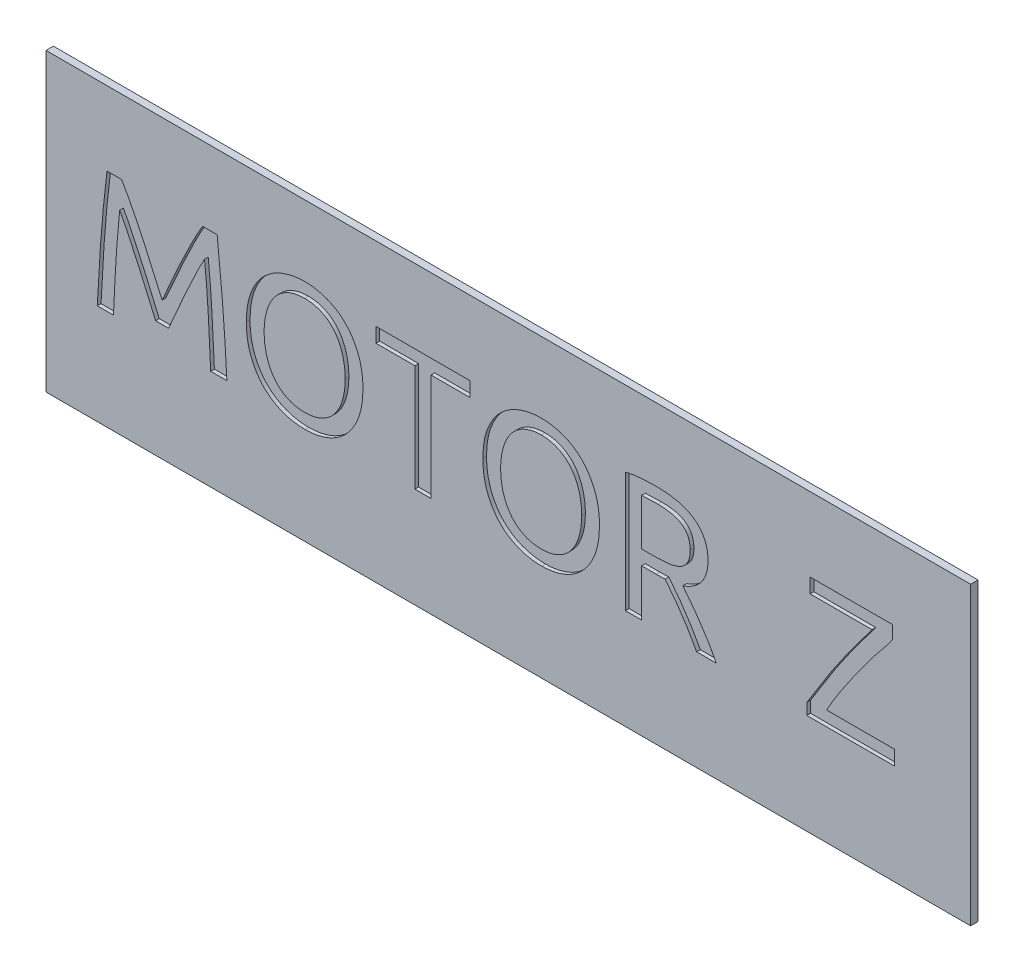
SolidWorks part; units mm, degrees
ref_plane "Front Plane" through (0, 0, 0) normal (0, 0, 1) x (1, 0, 0)
ref_plane "Top Plane" through (0, 0, 0) normal (0, 1, 0) x (1, 0, 0)
ref_plane "Right Plane" through (0, 0, 0) normal (1, 0, 0) x (0, 0, -1)
sketch "Sketch1" plane through (0, 0, 0) normal (0, 0, 1) x (1, 0, 0)
  line L1 (12.5, -4) -> (-12.5, -4)
  line L2 (12.5, -4) -> (12.5, 4)
  line L3 (12.5, 4) -> (-12.5, 4)
  line L4 (-12.5, -4) -> (-12.5, 4)
  line L5 (12.5, -4) -> (-12.5, 4) construction
  line L6 (12.5, 4) -> (-12.5, -4) construction
  point P0 (0, 0)
  dimension "D1" = 8
  dimension "D2" = 25
extrude "Boss-Extrude1" add sketch "Sketch1" along normal mid plane 0.2
sketch "Sketch2" plane through (0, 0, 0.1) normal (0, 0, 1) x (1, 0, 0)
  text T0 "LASER" font "Ubuntu" height in points 12
extrude "Cut-Extrude1" [suppressed] cut sketch "Sketch2" against normal blind 0.1
sketch "Sketch3" plane through (0, 0, 0.1) normal (0, 0, 1) x (1, 0, 0)
  text T0 "MOTOR  X" font "Ubuntu" height in points 12
extrude "Cut-Extrude2" [suppressed] cut sketch "Sketch3" against normal blind 0.1
sketch "Sketch4" [suppressed] plane through (0, 0, 0.1) normal (0, 0, 1) x (1, 0, 0)
  text T0 "MOTOR  Y" font "Ubuntu" height in points 12
extrude "Cut-Extrude3" [suppressed] cut sketch "Sketch4" against normal blind 0.1
sketch "Sketch5" [suppressed] plane through (0, 0, 0.1) normal (0, 0, 1) x (1, 0, 0)
  text T0 "Edge Sensors" font "Ubuntu" height in points 12
extrude "Cut-Extrude4" [suppressed] cut sketch "Sketch5" against normal blind 0.1
sketch "Sketch6" [suppressed] plane through (0, 0, 0.1) normal (0, 0, 1) x (1, 0, 0)
  text T0 "ON  LASER  OFF" font "Ubuntu" height in points 12
extrude "Cut-Extrude5" [suppressed] cut sketch "Sketch6" against normal blind 0.1
sketch "Sketch7" [suppressed] plane through (0, 0, 0.1) normal (0, 0, 1) x (1, 0, 0)
  text T0 "ON  PWR  OFF" font "Ubuntu" height in points 12
extrude "Cut-Extrude6" [suppressed] cut sketch "Sketch7" against normal blind 0.1
sketch "Sketch9" plane through (0, 0, 0.1) normal (0, 0, 1) x (1, 0, 0)
  text T0 "MOTOR  Z" font "Ubuntu" height in points 12
extrude "Cut-Extrude7" cut sketch "Sketch9" against normal blind 0.1
